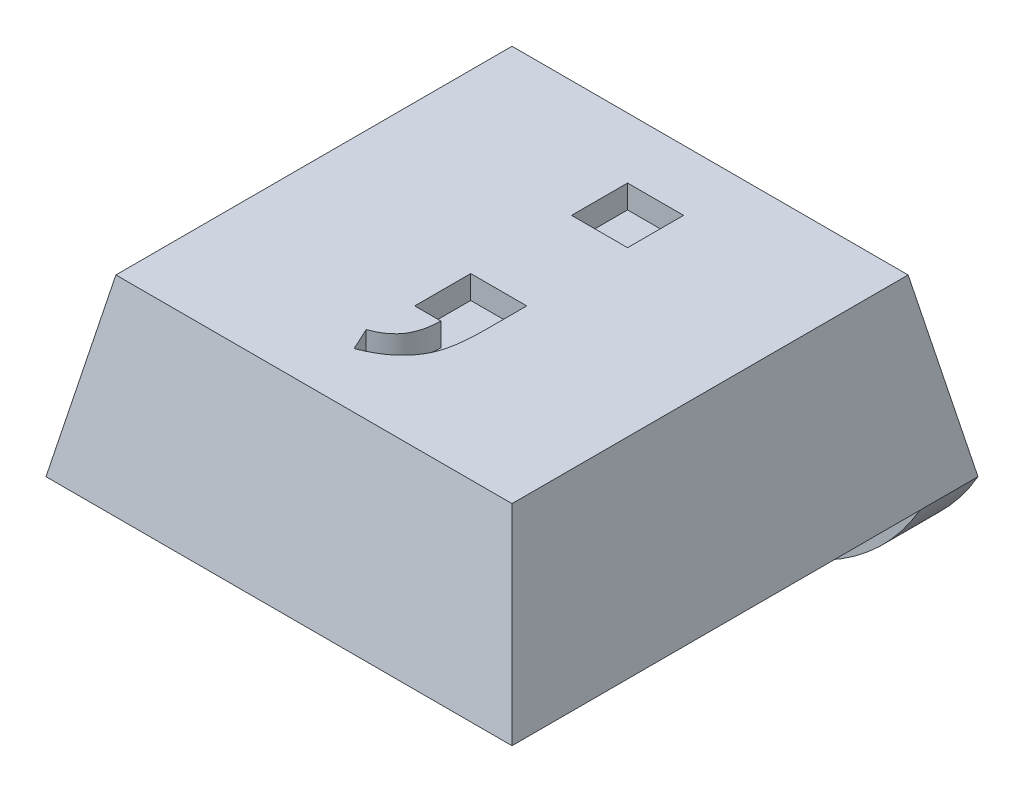
SolidWorks part; units mm, degrees
ref_plane "Front Plane" through (0, 0, 0) normal (0, 0, 1) x (1, 0, 0)
ref_plane "Top Plane" through (0, 0, 0) normal (0, 1, 0) x (1, 0, 0)
ref_plane "Right Plane" through (0, 0, 0) normal (1, 0, 0) x (0, 0, -1)
sketch "Sketch1" plane through (0, 0, 0) normal (0, 1, 0) x (1, 0, 0)
  line L1 (0, 0) -> (8, 0)
  line L2 (0, 0) -> (0, 8)
  line L3 (0, 8) -> (8, 8)
  line L4 (8, 0) -> (8, 8)
  dimension "D1" = 8
  dimension "D2" = 8
extrude "Boss-Extrude1" add sketch "Sketch1" along normal blind 3
sketch "Sketch2" plane through (0, 0, 0) normal (0, 0, 1) x (1, 0, 0)
  line L0 (0, 0) -> (0.6, 3)
  line L1 (0, 3) -> (8, 3) construction
  line L2 (0.6, 3) -> (0, 3)
  line L3 (0, 3) -> (0, 0)
  line L4 (8, 0) -> (7.4, 3)
  line L5 (7.4, 3) -> (8, 3)
  line L6 (8, 3) -> (8, 0)
  dimension "D1" = 0.6
  dimension "D2" = 0.6
extrude "Cut-Extrude1" cut sketch "Sketch2" against normal through all both and the other way through all
sketch "Sketch3" plane through (0, 0, 0) normal (1, 0, 0) x (0, 0, -1)
  line L0 (0, 0) -> (0.6, 3)
  line L1 (8, 3) -> (0, 3) construction
  line L2 (0.6, 3) -> (0, 3)
  line L3 (0, 3) -> (0, 0)
  line L4 (8, 3) -> (7.4, 3)
  line L5 (7.4, 3) -> (8, 0)
  line L6 (8, 3) -> (8, 0)
  dimension "D1" = 0.6
  dimension "D2" = 0.6
extrude "Cut-Extrude2" cut sketch "Sketch3" along normal blind 11
sketch "Sketch4" plane through (0, 0, 0) normal (0, -1, 0) x (1, 0, 0)
  line L0 (8, 0) -> (8, -8) construction
  line L3 (0, 0) -> (8, 0) construction
  circle A0 centre (4, -3.75) radius 1.75
  dimension "D1" = 3.5
  dimension "D2" = 4
  dimension "D3" = 3.75
extrude "Cut-Extrude3" cut sketch "Sketch4" against normal blind 0.4
sketch "Sketch5" plane through (0, 0, 0) normal (0, -1, 0) x (1, 0, 0)
  line L0 (8, 0) -> (8, -8) construction
  line L1 (0, -8) -> (8, -8)
  line L2 (0, -8) -> (0, -7)
  line L3 (0, -7) -> (8, -7)
  line L4 (8, -8) -> (8, -7)
  dimension "D1" = 1
extrude "Boss-Extrude2" add sketch "Sketch5" along normal blind 2
fillet "Fillet1" radius 4 2 edges at (8, -2, -7.5) (0, -2, -7.5)
sketch "Sketch6" plane through (0, 3, 0) normal (0, 1, 0) x (1, 0, 0)
  text T0 ";" font "Arial" height 5
extrude "Cut-Extrude4" cut sketch "Sketch6" against normal blind 0.4
